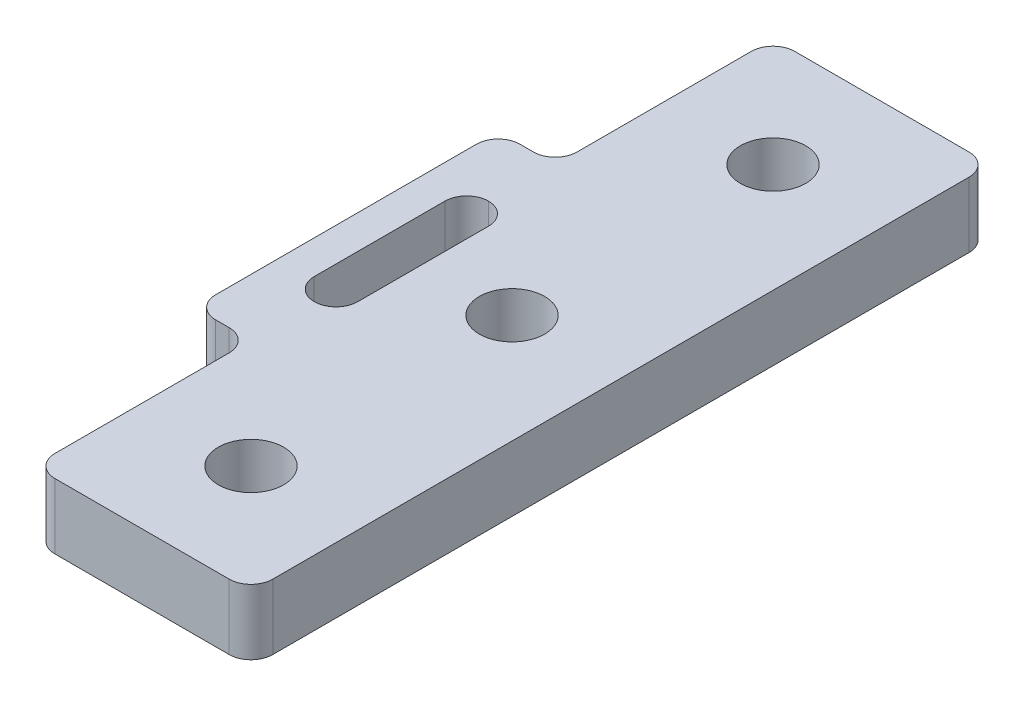
SolidWorks part; units mm, degrees
ref_plane "Front Plane" through (0, 0, 0) normal (0, 0, 1) x (1, 0, 0)
ref_plane "Top Plane" through (0, 0, 0) normal (0, 1, 0) x (1, 0, 0)
ref_plane "Right Plane" through (0, 0, 0) normal (1, 0, 0) x (0, 0, -1)
sketch "Sketch2" plane through (0, 0, 0) normal (0, 1, 0) x (1, 0, 0)
  line L0 (0, 0) -> (0, 13.97)
  line L6 (1.54, 10.985) -> (3.54, 10.985)
  line L7 (1.54, 10.985) -> (1.54, 2.985)
  line L8 (1.54, 2.985) -> (3.54, 2.985)
  line L9 (3.54, 10.985) -> (3.54, 2.985)
  line L18 (12.62, 13.97) -> (0, 13.97)
  line L22 (12.62, 13.97) -> (12.62, 0)
  line L23 (12.62, 0) -> (0, 0)
  line L25 (12.62, 0) -> (2.62, 0)
  line L26 (12.62, 0) -> (12.62, -10)
  line L27 (12.62, -10) -> (2.62, -10)
  line L28 (2.62, 0) -> (2.62, -10)
  line L29 (12.62, 13.97) -> (2.62, 13.97)
  line L30 (12.62, 13.97) -> (12.62, 23.97)
  line L31 (12.62, 23.97) -> (2.62, 23.97)
  line L32 (2.62, 13.97) -> (2.62, 23.97)
  circle A0 centre (7.62, 6.985) radius 1.5
  circle A1 centre (7.62, -5) radius 1.5
  circle A2 centre (7.62, 18.97) radius 1.5
  dimension "D2" = 3
  dimension "D3" = 5
  dimension "D11" = 10
  dimension "D12" = 10
  dimension "D14" = 3
  dimension "D16" = 3
  dimension "D1" = 6.985
  dimension "D4" = 13.97
  dimension "D5" = 8
  dimension "D6" = 2
  dimension "D7" = 4.08
  dimension "D8" = 2.985
  dimension "D9" = 7.62
  dimension "D10" = 10
  dimension "D13" = 10
  dimension "D15" = 5
  dimension "D17" = 5
extrude "Boss-Extrude1" add sketch "Sketch2" along normal blind 3 contours L23 L28 L27 L26 A1 | L23 L22 L18 L0 A0 L6 L9 L8 L7 | L32 L18 L30 L31 A2 region at (0.1883, 0, -6.985) region at (7.62, 0, 0.1414) region at (2.7614, 0, -18.97)
fillet "Fillet2" radius 1 4 edges at (1.54, 1.5, -2.985) (3.54, 1.5, -2.985) (3.54, 1.5, -10.985) (1.54, 1.5, -10.985)
fillet "Fillet3" radius 1 8 edges at (12.62, 1.5, 10) (2.62, 1.5, 10) (2.62, 1.5, 0) (0, 1.5, 0) (0, 1.5, -13.97) (2.62, 1.5, -13.97) (12.62, 1.5, -23.97) (2.62, 1.5, -23.97)
